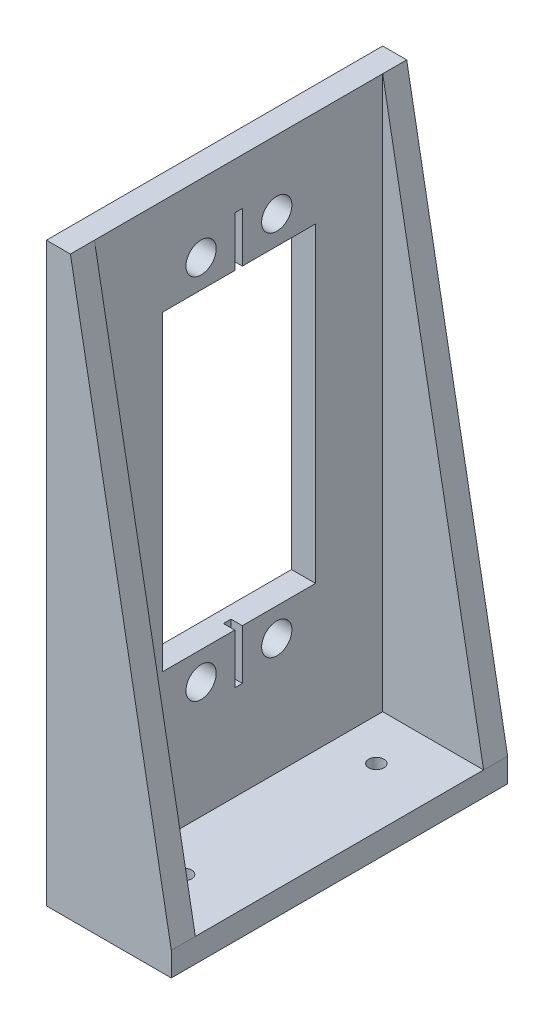
SolidWorks part; units mm, degrees
ref_plane "Front Plane" through (0, 0, 0) normal (0, 0, 1) x (1, 0, 0)
ref_plane "Top Plane" through (0, 0, 0) normal (0, 1, 0) x (1, 0, 0)
ref_plane "Right Plane" through (0, 0, 0) normal (1, 0, 0) x (0, 0, -1)
sketch "Sketch1" plane through (0, 0, 0) normal (0, 0, 1) x (1, 0, 0)
  line L0 (0, 0) -> (0, 76.2)
  line L1 (0, 76.2) -> (3.175, 76.2)
  line L2 (3.175, 76.2) -> (3.175, 3.175)
  line L3 (3.175, 3.175) -> (16.51, 3.175)
  line L4 (16.51, 3.175) -> (16.51, 0)
  line L5 (16.51, 0) -> (0, 0)
  dimension "D1" = 3.175
  dimension "D2" = 3.175
  dimension "D3" = 16.51
  dimension "D4" = 76.2
extrude "Boss-Extrude1" add sketch "Sketch1" along normal mid plane 44.45
sketch "Sketch3" plane through (0, 0, 22.225) normal (0, 0, 1) x (1, 0, 0)
  line L0 (3.175, 76.2) -> (16.51, 3.175)
  line L1 (16.51, 3.175) -> (3.175, 3.175)
  line L2 (3.175, 3.175) -> (3.175, 76.2)
extrude "Boss-Extrude2" add sketch "Sketch3" against normal blind 3.175
mirror "Mirror1" about plane through (0, 0, 0) normal (0, 0, 1) of "Boss-Extrude2"
sketch "Sketch4" plane through (0, 3.175, 0) normal (0, 1, 0) x (1, 0, 0)
  line L1 (3.175, 19.05) -> (16.51, 19.05) construction
  line L3 (3.175, 0) -> (16.51, 0) construction
  line L4 (3.175, -19.05) -> (3.175, 19.05) construction
  line L5 (16.51, -19.05) -> (16.51, 19.05) construction
  circle A0 centre (8.68, 12.7) radius 1
  circle A3 centre (8.68, -12.7) radius 1
  dimension "D1" = 2
  dimension "D2" = 6.35
  dimension "D3" = 5.505
extrude "Cut-Extrude2" cut sketch "Sketch4" against normal through all
sketch "Sketch5" plane through (3.175, 0, 0) normal (1, 0, 0) x (0, 0, -1)
  line L0 (-19.05, 76.2) -> (-19.05, 3.175) construction
  line L1 (-19.05, 3.175) -> (19.05, 3.175) construction
  circle A0 centre (-4.953, 18.575) radius 2
  circle A1 centre (5.047, 18.575) radius 2
  circle A2 centre (-4.953, 67.175) radius 2
  circle A3 centre (5.047, 67.175) radius 2
  dimension "D3" = 4
  dimension "D5" = 4
  dimension "D7" = 4
  dimension "D8" = 4
  dimension "D1" = 14.097
  dimension "D2" = 15.4
  dimension "D4" = 10
  dimension "D6" = 48.6
extrude "Cut-Extrude3" cut sketch "Sketch5" against normal through all
sketch "Sketch6" plane through (3.175, 0, 0) normal (1, 0, 0) x (0, 0, -1)
  line L0 (-10.08, 63.452) -> (10.174, 22.298) construction
  line L1 (-10.08, 63.452) -> (10.174, 63.452)
  line L2 (-10.08, 63.452) -> (-10.08, 22.298)
  line L3 (-10.08, 22.298) -> (10.174, 22.298)
  line L4 (10.174, 63.452) -> (10.174, 22.298)
  line L5 (10.174, 63.452) -> (-10.08, 22.298) construction
  line L6 (-4.953, 67.175) -> (5.047, 18.575) construction
  line L7 (-4.953, 18.575) -> (5.047, 67.175) construction
  point P12 (0.047, 42.875)
  point P13 (0.047, 42.875)
  dimension "D1" = 41.154
  dimension "D2" = 20.254
extrude "Cut-Extrude4" cut sketch "Sketch6" against normal through all
sketch "Sketch7" plane through (0, 63.452, 0) normal (0, -1, 0) x (1, 0, 0)
  line L0 (3.175, -10.174) -> (3.175, 10.08) construction
  line L1 (1.675, -0.5) -> (3.175, -0.5)
  line L2 (1.675, -0.5) -> (1.675, 0.5)
  line L3 (1.675, 0.5) -> (3.175, 0.5)
  line L4 (3.175, -0.5) -> (3.175, 0.5)
  line L5 (1.675, -0.5) -> (3.175, 0.5) construction
  line L6 (1.675, 0.5) -> (3.175, -0.5) construction
  line L7 (9.0805, 0) -> (-9.0805, 0) construction
  point P0 (2.425, 0)
  dimension "D1" = 1
  dimension "D2" = 1.5
extrude "Cut-Extrude5" cut sketch "Sketch7" against normal blind 6.604
extrude "Cut-Extrude6" cut sketch "Sketch7<2>" along normal blind 6.604 from surface starting at face at (1.5875, 22.298, -0.047)
sketch "Sketch7<2>" plane through (0, 63.452, 0) normal (0, -1, 0) x (1, 0, 0) same geometry as "Sketch7"
equation "\"D1@Sketch4\"=2mm"
equation "\"tightTol\"= 0.005in"
equation "\"normTol\"= 0.01in"
equation "\"looseTol\"= 0.02in"
equation "\"D2@Sketch5\"=0.5in+2.7mm"
equation "\"D3@Sketch5\"=4mm"
equation "\"D4@Sketch5\"=10mm"
equation "\"D5@Sketch5\"=4mm"
equation "\"D6@Sketch5\"=48.6mm"
equation "\"D8@Sketch5\"=4mm"
equation "\"D1@Sketch6\" = 40.9mm + \"normTol\""
equation "\"D2@Sketch6\" = 20mm + \"normTol\""
equation "\"D1@Sketch7\"=1mm"
equation "\"D2@Sketch7\"=1.5mm"
equation "\"D7@Sketch5\"=4mm"
equation "\"D3@Sketch4\"=0.125000in+2.33mm"
